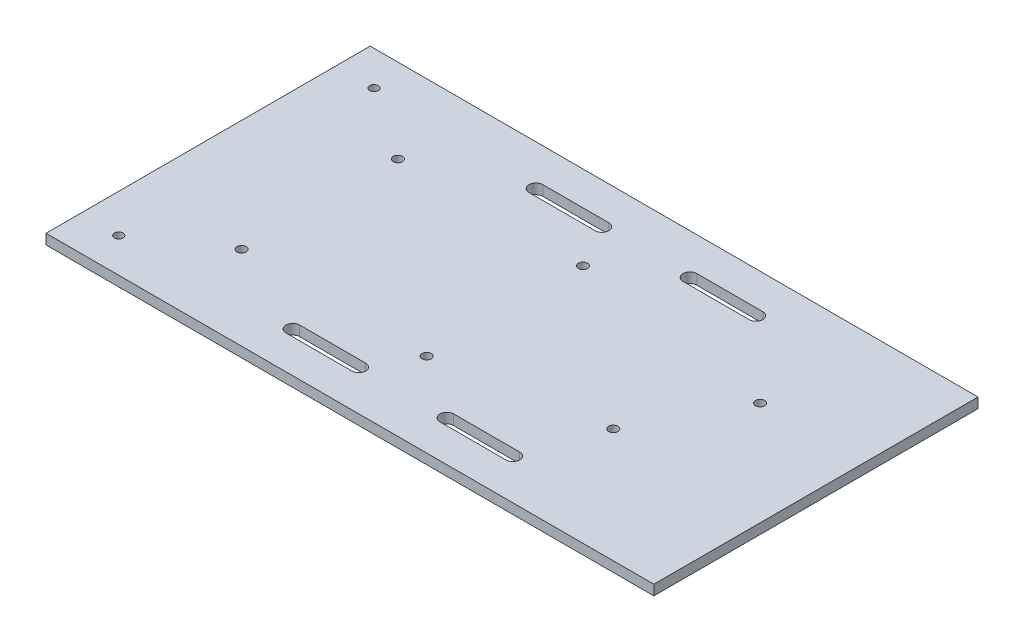
SolidWorks part; units mm, degrees
ref_plane "Front Plane" through (0, 0, 0) normal (0, 0, 1) x (1, 0, 0)
ref_plane "Top Plane" through (0, 0, 0) normal (0, 1, 0) x (1, 0, 0)
ref_plane "Right Plane" through (0, 0, 0) normal (1, 0, 0) x (0, 0, -1)
sketch "Sketch1" plane through (0, 0, 0) normal (0, 1, 0) x (1, 0, 0)
  line L0 (0, 0) -> (190.5, 0) construction
  line L1 (0, 50.8) -> (190.5, 50.8)
  line L2 (0, 50.8) -> (0, -50.8)
  line L3 (0, -50.8) -> (190.5, -50.8)
  line L4 (190.5, 50.8) -> (190.5, -50.8)
  line L5 (0, 50.8) -> (190.5, -50.8) construction
  line L6 (0, -50.8) -> (190.5, 50.8) construction
  point P0 (11.3289, 32.4526)
  point P5 (0, 0)
  dimension "D1" = 101.6
  dimension "D2" = 190.5
extrude "plate" add sketch "Sketch1" along normal blind 3.175
hole_wizard "pi holes" positions "Sketch4" profile "Sketch5" hole size "M2.5" standard "ISO" end condition through all
sketch "Sketch4" plane through (0, 3.175, 0) normal (0, 1, 0) x (1, 0, 0)
  line L0 (0, 0) -> (190.5, 0) construction
  line L1 (190.5, -50.8) -> (190.5, 50.8) construction
  line L3 (93, 24.5) -> (35, 24.5) construction
  line L5 (93, -24.5) -> (35, -24.5) construction
  line L6 (0, 50.8) -> (0, -50.8) construction
  point P0 (93, 24.5)
  point P2 (35, 24.5)
  point P18 (35, -24.5)
  point P19 (93, -24.5)
  point P20 (0, 0)
  point P21 (0, 0)
  point P22 (0, 0)
  point P23 (0, 0)
  point P24 (0, 0)
  point P25 (0, 0)
  point P26 (0, 0)
  dimension "D1" = 58
  dimension "D2" = 24.5
  dimension "D3" = 35
sketch "Sketch5" plane through (93, 3.175, -24.5) normal (1, 0, 0) x (0, 0, 1)
  line L0 (0, 0) -> (0, 3.175)
  line L1 (0, 3.175) -> (1.45, 3.175)
  line L2 (1.45, 3.175) -> (1.45, 0)
  line L5 (1.45, 0) -> (0, 0)
  line L11 (0, -6.35) -> (0, 107.95) construction
  dimension "Thru Hole Dia." = 2.9
  dimension "Thru Hole Depth" = 3.175
hole_wizard "regulator holes" positions "Sketch6" profile "Sketch7" hole size "M2.5" standard "ISO" end condition through all
sketch "Sketch6" plane through (0, 3.175, 0) normal (0, 1, 0) x (1, 0, 0)
  line L1 (0, 0) -> (190.5, 0) construction
  line L2 (190.5, -50.8) -> (190.5, 50.8) construction
  line L5 (142, -15) -> (158, -15) construction
  line L6 (142, -15) -> (142, 15) construction
  line L7 (142, 15) -> (158, 15) construction
  line L8 (158, -15) -> (158, 15) construction
  line L11 (0, 50.8) -> (0, -50.8) construction
  point P2 (158, 15)
  point P6 (142, -15)
  point P131 (0, 0)
  point P132 (142, 0)
  point P133 (158, 0)
  dimension "D1" = 16
  dimension "D2" = 30
  dimension "D3" = 142
sketch "Sketch7" plane through (158, 3.175, -15) normal (1, 0, 0) x (0, 0, 1)
  line L0 (0, 0) -> (0, 3.175)
  line L1 (0, 3.175) -> (1.45, 3.175)
  line L2 (1.45, 3.175) -> (1.45, 0)
  line L5 (1.45, 0) -> (0, 0)
  line L11 (0, -6.35) -> (0, 107.95) construction
  dimension "Thru Hole Dia." = 2.9
  dimension "Thru Hole Depth" = 3.175
hole_wizard "mount slots" positions "Sketch8" profile "Sketch9" size "M4" standard "ISO" slot yes end condition through all
sketch "Sketch8" plane through (0, 3.175, 0) normal (0, 1, 0) x (1, 0, 0)
  line L0 (75, 38.1) -> (123.26, 38.1) construction
  line L2 (0, 0) -> (190.5, 0) construction
  line L3 (190.5, -50.8) -> (190.5, 50.8) construction
  line L4 (0, 50.8) -> (0, -50.8) construction
  line L5 (75, -38.1) -> (123.26, -38.1) construction
  line L6 (62.5, 38.1) -> (87.5, 38.1) construction
  point P1 (75, 38.1)
  point P2 (123.26, 38.1)
  point P17 (0, 0)
  point P18 (0, 0)
  point P23 (123.26, -38.1)
  point P24 (75, -38.1)
  dimension "D1" = 48.26
  dimension "D2" = 38.1
  dimension "D3" = 75
  dimension "D4" = 25
sketch "Sketch9" plane through (75, 3.175, -38.1) normal (1, 0, 0) x (0, 0, 1)
  line L0 (0, 0) -> (0, 3.175)
  line L1 (0, 3.175) -> (2.15, 3.175)
  line L2 (2.15, 3.175) -> (2.15, 0)
  line L5 (2.15, 0) -> (0, 0)
  line L11 (0, -6.35) -> (0, 107.95) construction
  dimension "Thru Hole Dia." = 4.3
  dimension "Thru Hole Depth" = 3.175
hole_wizard "bracket  holes" positions "Sketch10" profile "Sketch11" hole size "M2.5" standard "ISO" end condition through all
sketch "Sketch10" plane through (0, 3.175, 0) normal (0, 1, 0) x (1, 0, 0)
  line L0 (0, 0) -> (190.5, 0) construction
  line L1 (0, 50.8) -> (0, -50.8) construction
  line L2 (190.5, -50.8) -> (190.5, 50.8) construction
  point P0 (12, 40)
  point P11 (0, 0)
  point P14 (12, -40)
  dimension "D1" = 12
  dimension "D2" = 40
sketch "Sketch11" plane through (12, 3.175, -40) normal (1, 0, 0) x (0, 0, 1)
  line L0 (0, 0) -> (0, 3.175)
  line L1 (0, 3.175) -> (1.35, 3.175)
  line L2 (1.35, 3.175) -> (1.35, 0)
  line L5 (1.35, 0) -> (0, 0)
  line L11 (0, -6.35) -> (0, 107.95) construction
  dimension "Thru Hole Dia." = 2.7
  dimension "Thru Hole Depth" = 3.175
